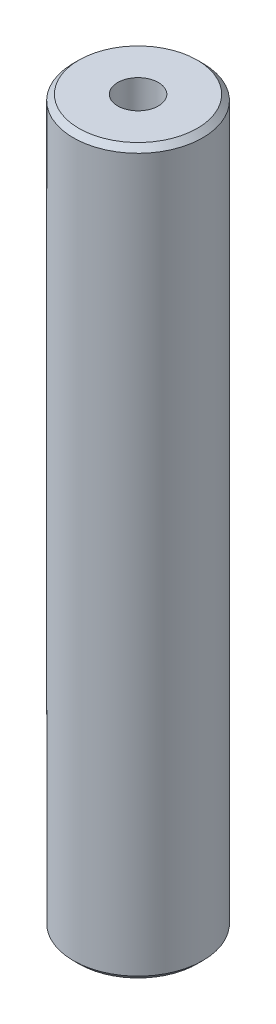
SolidWorks part; units mm, degrees
ref_plane "Front Plane" through (0, 0, 0) normal (0, 0, 1) x (1, 0, 0)
ref_plane "Top Plane" through (0, 0, 0) normal (0, 1, 0) x (1, 0, 0)
ref_plane "Right Plane" through (0, 0, 0) normal (1, 0, 0) x (0, 0, -1)
sketch "Sketch1" plane through (0, 0, 0) normal (0, 1, 0) x (1, 0, 0)
  circle A0 centre (0, 0) radius 15
  dimension "SHAFT_OD" = 30
extrude "Boss-Extrude1" add sketch "Sketch1" along normal blind 167.896
sketch "Sketch2" plane through (0, 0, 0) normal (0, 1, 0) x (1, 0, 0)
  circle A0 centre (0, 0) radius 4.7241
  dimension "BORE_D" = 9.4483
extrude "Cut-Extrude1" cut sketch "Sketch2" along normal through all
chamfer "Chamfer1" distance 1.2677 angle 45 2 edges at (0, 167.896, 15) (0, 0, 15)
